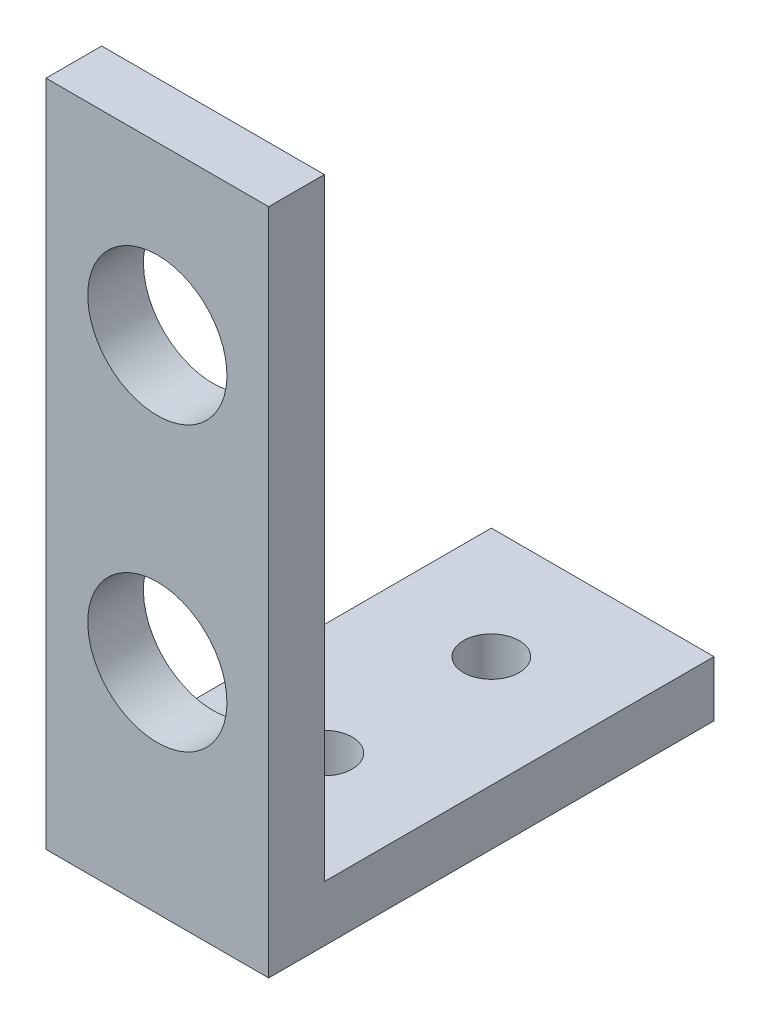
SolidWorks part; units mm, degrees
ref_plane "Front Plane" through (0, 0, 0) normal (0, 0, 1) x (1, 0, 0)
ref_plane "Top Plane" through (0, 0, 0) normal (0, 1, 0) x (1, 0, 0)
ref_plane "Right Plane" through (0, 0, 0) normal (1, 0, 0) x (0, 0, -1)
sketch "Sketch1" plane through (0, 0, 0) normal (1, 0, 0) x (0, 0, -1)
  line L0 (0, 76.2) -> (0, 0)
  line L1 (0, 0) -> (50.8, 0)
  line L2 (6.35, 76.2) -> (6.35, 6.35)
  line L3 (6.35, 6.35) -> (50.8, 6.35)
  line L4 (0, 76.2) -> (6.35, 76.2)
  line L5 (50.8, 6.35) -> (50.8, 0)
  dimension "D1" = 76.2
  dimension "D2" = 50.8
  dimension "D3" = 6.35
extrude "Boss-Extrude1" add sketch "Sketch1" along normal blind 25.4
sketch "Sketch2" plane through (0, 6.35, 0) normal (0, 1, 0) x (1, 0, 0)
  line L1 (25.4, 6.35) -> (0, 6.35) construction
  circle A0 centre (12.7, 38.1) radius 3.175
  circle A1 centre (12.7, 19.05) radius 3.175
  dimension "D1" = 12.7
  dimension "D2" = 31.75
  dimension "D3" = 6.35
extrude "Cut-Extrude1" cut sketch "Sketch2" against normal up to next
hole_wizard "5/8 (0.625) Diameter Hole1" positions "Sketch4" profile "Sketch3" hole size "5/8" standard "ANSI Inch" end condition up to next
sketch "Sketch4" plane through (0, 0, -6.35) normal (0, 0, -1) x (-1, 0, 0)
  line L0 (-25.4, 0) -> (0, 0) construction
  line L1 (-25.4, 6.35) -> (-25.4, 76.2) construction
  point P0 (-12.7, 57.15)
  point P2 (-12.7, 24.8412)
  dimension "D1" = 57.15
  dimension "D2" = 12.7
  dimension "D3" = 24.8412
  dimension "D4" = 12.7
sketch "Sketch3" plane through (12.7, 57.15, -6.35) normal (1, 0, 0) x (0, 1, 0)
  line L0 (0, 0) -> (0, 6.35)
  line L1 (0, 6.35) -> (7.9375, 6.35)
  line L2 (7.9375, 6.35) -> (7.9375, 0)
  line L5 (7.9375, 0) -> (0, 0)
  line L11 (0, -6.35) -> (0, 107.95) construction
  dimension "Thru Hole Dia." = 15.875
  dimension "Thru Hole Depth" = 6.35
